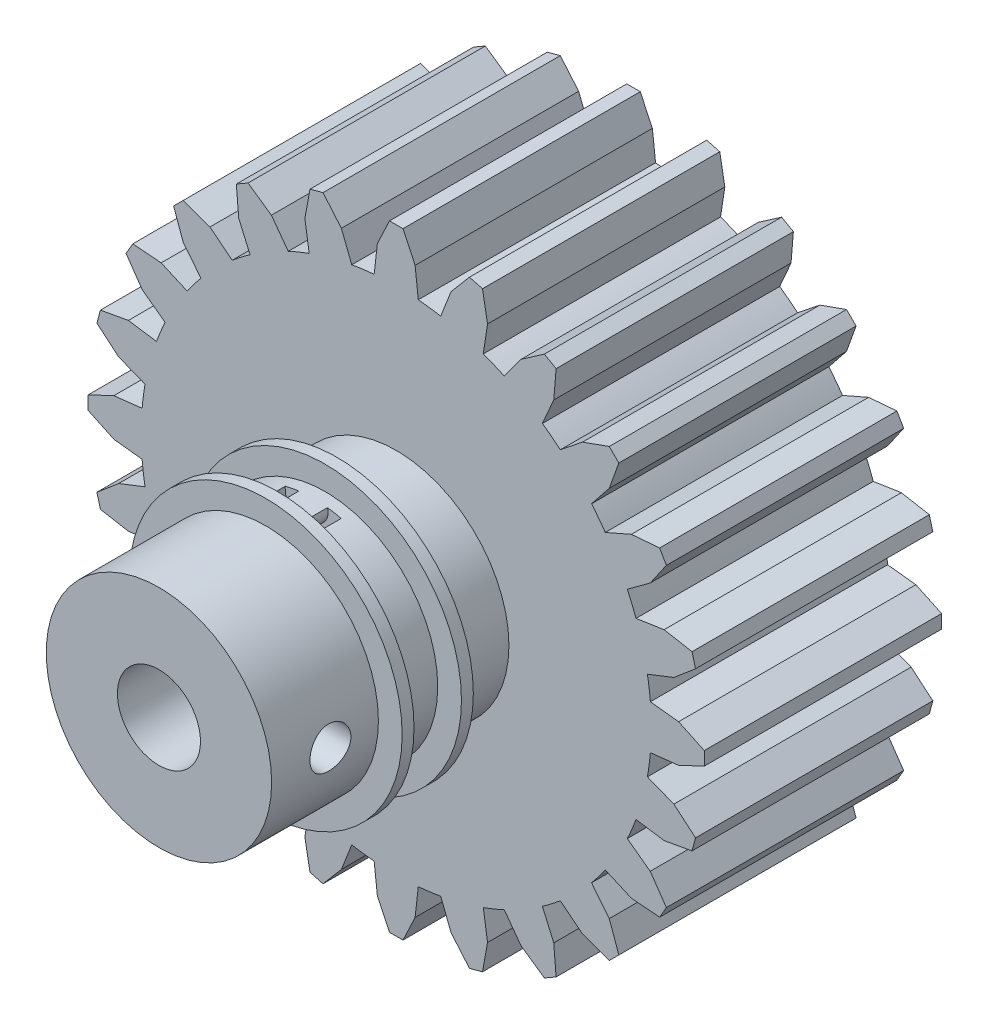
SolidWorks part; units mm, degrees
ref_plane "Plan de face" through (0, 0, 0) normal (0, 0, 1) x (1, 0, 0)
ref_plane "Plan de dessus" through (0, 0, 0) normal (0, 1, 0) x (1, 0, 0)
ref_plane "Plan de droite" through (0, 0, 0) normal (1, 0, 0) x (0, 0, -1)
sketch "Esquisse1" plane through (0, 0, 0) normal (0, 0, 1) x (1, 0, 0)
  line L0 (-1.8585, 21.4195) -> (-1.5915, 23.7996)
  line L1 (0, 2.2889) -> (0, 19223.5431) construction
  line L2 (-1.5915, 23.7996) -> (-0.5695, 25.9656)
  line L3 (-0.5695, 25.9656) -> (0.5695, 25.9656)
  line L4 (0, 0) -> (50000, 0) construction
  line L5 (1.8585, 21.4195) -> (1.5915, 23.7996)
  line L6 (1.5915, 23.7996) -> (0.5695, 25.9656)
  line L7 (3.7486, 21.1707) -> (4.6225, 23.4006)
  line L8 (4.6225, 23.4006) -> (6.1703, 25.2282)
  line L9 (7.6971, 22.5767) -> (7.2705, 24.9334)
  line L10 (7.339, 20.2087) -> (7.6971, 22.5767)
  line L11 (6.1703, 25.2282) -> (7.2705, 24.9334)
  line L12 (9.1003, 19.4791) -> (10.5215, 21.4068)
  line L13 (10.5215, 21.4068) -> (12.4896, 22.7716)
  line L14 (13.2781, 19.8153) -> (13.476, 22.2021)
  line L15 (12.3193, 17.6206) -> (13.2781, 19.8153)
  line L16 (12.4896, 22.7716) -> (13.476, 22.2021)
  line L17 (13.8317, 16.46) -> (15.7035, 17.9542)
  line L18 (15.7035, 17.9542) -> (17.9577, 18.7631)
  line L19 (17.9542, 15.7035) -> (18.7631, 17.9577)
  line L20 (16.46, 13.8317) -> (17.9542, 15.7035)
  line L21 (17.9577, 18.7631) -> (18.7631, 17.9577)
  line L22 (17.6206, 12.3193) -> (19.8153, 13.2781)
  line L23 (19.8153, 13.2781) -> (22.2021, 13.476)
  line L24 (21.4068, 10.5215) -> (22.7716, 12.4896)
  line L25 (19.4791, 9.1003) -> (21.4068, 10.5215)
  line L26 (22.2021, 13.476) -> (22.7716, 12.4896)
  line L27 (20.2087, 7.339) -> (22.5767, 7.6971)
  line L28 (22.5767, 7.6971) -> (24.9334, 7.2705)
  line L29 (23.4006, 4.6225) -> (25.2282, 6.1703)
  line L30 (21.1707, 3.7486) -> (23.4006, 4.6225)
  line L31 (24.9334, 7.2705) -> (25.2282, 6.1703)
  line L32 (21.4195, 1.8585) -> (23.7996, 1.5915)
  line L33 (23.7996, 1.5915) -> (25.9656, 0.5695)
  line L34 (23.7996, -1.5915) -> (25.9656, -0.5695)
  line L35 (21.4195, -1.8585) -> (23.7996, -1.5915)
  line L36 (25.9656, 0.5695) -> (25.9656, -0.5695)
  line L37 (21.1707, -3.7486) -> (23.4006, -4.6225)
  line L38 (23.4006, -4.6225) -> (25.2282, -6.1703)
  line L39 (22.5767, -7.6971) -> (24.9334, -7.2705)
  line L40 (20.2087, -7.339) -> (22.5767, -7.6971)
  line L41 (25.2282, -6.1703) -> (24.9334, -7.2705)
  line L42 (19.4791, -9.1003) -> (21.4068, -10.5215)
  line L43 (21.4068, -10.5215) -> (22.7716, -12.4896)
  line L44 (19.8153, -13.2781) -> (22.2021, -13.476)
  line L45 (17.6206, -12.3193) -> (19.8153, -13.2781)
  line L46 (22.7716, -12.4896) -> (22.2021, -13.476)
  line L47 (16.46, -13.8317) -> (17.9542, -15.7035)
  line L48 (17.9542, -15.7035) -> (18.7631, -17.9577)
  line L49 (15.7035, -17.9542) -> (17.9577, -18.7631)
  line L50 (13.8317, -16.46) -> (15.7035, -17.9542)
  line L51 (18.7631, -17.9577) -> (17.9577, -18.7631)
  line L52 (12.3193, -17.6206) -> (13.2781, -19.8153)
  line L53 (13.2781, -19.8153) -> (13.476, -22.2021)
  line L54 (10.5215, -21.4068) -> (12.4896, -22.7716)
  line L55 (9.1003, -19.4791) -> (10.5215, -21.4068)
  line L56 (13.476, -22.2021) -> (12.4896, -22.7716)
  line L57 (7.339, -20.2087) -> (7.6971, -22.5767)
  line L58 (7.6971, -22.5767) -> (7.2705, -24.9334)
  line L59 (4.6225, -23.4006) -> (6.1703, -25.2282)
  line L60 (3.7486, -21.1707) -> (4.6225, -23.4006)
  line L61 (7.2705, -24.9334) -> (6.1703, -25.2282)
  line L62 (1.8585, -21.4195) -> (1.5915, -23.7996)
  line L63 (1.5915, -23.7996) -> (0.5695, -25.9656)
  line L64 (-1.5915, -23.7996) -> (-0.5695, -25.9656)
  line L65 (-1.8585, -21.4195) -> (-1.5915, -23.7996)
  line L66 (0.5695, -25.9656) -> (-0.5695, -25.9656)
  line L67 (-3.7486, -21.1707) -> (-4.6225, -23.4006)
  line L68 (-4.6225, -23.4006) -> (-6.1703, -25.2282)
  line L69 (-7.6971, -22.5767) -> (-7.2705, -24.9334)
  line L70 (-7.339, -20.2087) -> (-7.6971, -22.5767)
  line L71 (-6.1703, -25.2282) -> (-7.2705, -24.9334)
  line L72 (-9.1003, -19.4791) -> (-10.5215, -21.4068)
  line L73 (-10.5215, -21.4068) -> (-12.4896, -22.7716)
  line L74 (-13.2781, -19.8153) -> (-13.476, -22.2021)
  line L75 (-12.3193, -17.6206) -> (-13.2781, -19.8153)
  line L76 (-12.4896, -22.7716) -> (-13.476, -22.2021)
  line L77 (-13.8317, -16.46) -> (-15.7035, -17.9542)
  line L78 (-15.7035, -17.9542) -> (-17.9577, -18.7631)
  line L79 (-17.9542, -15.7035) -> (-18.7631, -17.9577)
  line L80 (-16.46, -13.8317) -> (-17.9542, -15.7035)
  line L81 (-17.9577, -18.7631) -> (-18.7631, -17.9577)
  line L82 (-17.6206, -12.3193) -> (-19.8153, -13.2781)
  line L83 (-19.8153, -13.2781) -> (-22.2021, -13.476)
  line L84 (-21.4068, -10.5215) -> (-22.7716, -12.4896)
  line L85 (-19.4791, -9.1003) -> (-21.4068, -10.5215)
  line L86 (-22.2021, -13.476) -> (-22.7716, -12.4896)
  line L87 (-20.2087, -7.339) -> (-22.5767, -7.6971)
  line L88 (-22.5767, -7.6971) -> (-24.9334, -7.2705)
  line L89 (-23.4006, -4.6225) -> (-25.2282, -6.1703)
  line L90 (-21.1707, -3.7486) -> (-23.4006, -4.6225)
  line L91 (-24.9334, -7.2705) -> (-25.2282, -6.1703)
  line L92 (-21.4195, -1.8585) -> (-23.7996, -1.5915)
  line L93 (-23.7996, -1.5915) -> (-25.9656, -0.5695)
  line L94 (-23.7996, 1.5915) -> (-25.9656, 0.5695)
  line L95 (-21.4195, 1.8585) -> (-23.7996, 1.5915)
  line L96 (-25.9656, -0.5695) -> (-25.9656, 0.5695)
  line L97 (-21.1707, 3.7486) -> (-23.4006, 4.6225)
  line L98 (-23.4006, 4.6225) -> (-25.2282, 6.1703)
  line L99 (-22.5767, 7.6971) -> (-24.9334, 7.2705)
  line L100 (-20.2087, 7.339) -> (-22.5767, 7.6971)
  line L101 (-25.2282, 6.1703) -> (-24.9334, 7.2705)
  line L102 (-19.4791, 9.1003) -> (-21.4068, 10.5215)
  line L103 (-21.4068, 10.5215) -> (-22.7716, 12.4896)
  line L104 (-19.8153, 13.2781) -> (-22.2021, 13.476)
  line L105 (-17.6206, 12.3193) -> (-19.8153, 13.2781)
  line L106 (-22.7716, 12.4896) -> (-22.2021, 13.476)
  line L107 (-16.46, 13.8317) -> (-17.9542, 15.7035)
  line L108 (-17.9542, 15.7035) -> (-18.7631, 17.9577)
  line L109 (-15.7035, 17.9542) -> (-17.9577, 18.7631)
  line L110 (-13.8317, 16.46) -> (-15.7035, 17.9542)
  line L111 (-18.7631, 17.9577) -> (-17.9577, 18.7631)
  line L112 (-12.3193, 17.6206) -> (-13.2781, 19.8153)
  line L113 (-13.2781, 19.8153) -> (-13.476, 22.2021)
  line L114 (-10.5215, 21.4068) -> (-12.4896, 22.7716)
  line L115 (-9.1003, 19.4791) -> (-10.5215, 21.4068)
  line L116 (-13.476, 22.2021) -> (-12.4896, 22.7716)
  line L117 (-7.339, 20.2087) -> (-7.6971, 22.5767)
  line L118 (-7.6971, 22.5767) -> (-7.2705, 24.9334)
  line L119 (-4.6225, 23.4006) -> (-6.1703, 25.2282)
  line L120 (-3.7486, 21.1707) -> (-4.6225, 23.4006)
  line L121 (-7.2705, 24.9334) -> (-6.1703, 25.2282)
  arc A0 (-7.339, 20.2087) -> (-9.1003, 19.4791) centre (0, 0) ccw
  circle A1 centre (0, 0) radius 3.5
  arc A2 (-1.8585, 21.4195) -> (-3.7486, 21.1707) centre (0, 0) ccw
  arc A3 (3.7486, 21.1707) -> (1.8585, 21.4195) centre (0, 0) ccw
  arc A4 (9.1003, 19.4791) -> (7.339, 20.2087) centre (0, 0) ccw
  arc A5 (13.8317, 16.46) -> (12.3193, 17.6206) centre (0, 0) ccw
  arc A6 (17.6206, 12.3193) -> (16.46, 13.8317) centre (0, 0) ccw
  arc A7 (20.2087, 7.339) -> (19.4791, 9.1003) centre (0, 0) ccw
  arc A8 (21.4195, 1.8585) -> (21.1707, 3.7486) centre (0, 0) ccw
  arc A9 (21.1707, -3.7486) -> (21.4195, -1.8585) centre (0, 0) ccw
  arc A10 (19.4791, -9.1003) -> (20.2087, -7.339) centre (0, 0) ccw
  arc A11 (16.46, -13.8317) -> (17.6206, -12.3193) centre (0, 0) ccw
  arc A12 (12.3193, -17.6206) -> (13.8317, -16.46) centre (0, 0) ccw
  arc A13 (7.339, -20.2087) -> (9.1003, -19.4791) centre (0, 0) ccw
  arc A14 (1.8585, -21.4195) -> (3.7486, -21.1707) centre (0, 0) ccw
  arc A15 (-3.7486, -21.1707) -> (-1.8585, -21.4195) centre (0, 0) ccw
  arc A16 (-9.1003, -19.4791) -> (-7.339, -20.2087) centre (0, 0) ccw
  arc A17 (-13.8317, -16.46) -> (-12.3193, -17.6206) centre (0, 0) ccw
  arc A18 (-17.6206, -12.3193) -> (-16.46, -13.8317) centre (0, 0) ccw
  arc A19 (-20.2087, -7.339) -> (-19.4791, -9.1003) centre (0, 0) ccw
  arc A20 (-21.4195, -1.8585) -> (-21.1707, -3.7486) centre (0, 0) ccw
  arc A21 (-21.1707, 3.7486) -> (-21.4195, 1.8585) centre (0, 0) ccw
  arc A22 (-19.4791, 9.1003) -> (-20.2087, 7.339) centre (0, 0) ccw
  arc A23 (-16.46, 13.8317) -> (-17.6206, 12.3193) centre (0, 0) ccw
  arc A24 (-12.3193, 17.6206) -> (-13.8317, 16.46) centre (0, 0) ccw
  point P17 (0, 25.9656)
  point P156 (0, 0)
  dimension "D1" = 43
  dimension "D2" = 7
  dimension "D3" = 2.395
  dimension "D4" = 83.6
  dimension "D5" = 1.8585
  dimension "D6" = 2.395
  dimension "D7" = 0.5695
  dimension "D8" = 24
extrude "Boss.-Extru.1" add sketch "Esquisse1" along normal blind 20
sketch "Esquisse2" plane through (0, 0, 20) normal (0, 0, 1) x (1, 0, 0)
  circle A0 centre (0, 0) radius 3.5
  circle A1 centre (0, 0) radius 9.5
  circle A2 centre (0, 0) radius 3.5 construction
  dimension "D1" = 6
extrude "Boss.-Extru.2" add sketch "Esquisse2" along normal blind 20
sketch "Esquisse3" plane through (0, 0, 0) normal (1, 0, 0) x (0, -1, 0)
  line L0 (-7.5, -35.0467) -> (49992.5, -35.0467) construction
  line L2 (0, -30) -> (0, 49970) construction
  line L3 (-9.5, -40) -> (9.5, -40) construction
  circle A0 centre (0, -35.0467) radius 1.725
  point P13 (0, -40)
  dimension "D1" = 3.45
extrude "Enlèv. mat.-Extru.1" cut sketch "Esquisse3" along normal blind 10
ref_plane "Plan2" through (0, 0, 25) normal (0, 0, 1) x (1, 0, 0)
ref_plane "Plan3" through (0, 0, 30) normal (0, 0, 1) x (1, 0, 0)
sketch "Esquisse10" plane through (0, 0, 25) normal (0, 0, 1) x (1, 0, 0)
  circle A0 centre (0, 0) radius 11.5
  circle A1 centre (0, 0) radius 9.5
  dimension "D1" = 2
extrude "Boss.-Extru.6" add sketch "Esquisse10" along normal blind 1
sketch "Esquisse11" plane through (0, 0, 30) normal (0, 0, 1) x (1, 0, 0)
  circle A0 centre (0, 0) radius 11.5
  circle A1 centre (0, 0) radius 9.5
  dimension "D1" = 2
extrude "Boss.-Extru.7" add sketch "Esquisse11" along normal blind 1
sketch "Esquisse12" plane through (0, 0, 26) normal (0, 0, 1) x (1, 0, 0)
  circle A0 centre (0, 10.5) radius 0.5
  circle A2 centre (0, 0) radius 11.5 construction
  point P2 (0, 10.6729)
  dimension "D1" = 1
  dimension "D2" = 10.5
extrude "Boss.-Extru.8" [suppressed] add sketch "Esquisse12" along normal up to surface (4 mm away) up to face at (11.5, 0, 30)
sketch "Esquisse13" plane through (0, 0, 26) normal (0, 0, 1) x (1, 0, 0)
  line L0 (0, 0) -> (0, 23.2063) construction
  arc A0 (-1.2077, 9.4229) -> (1.2077, 9.4229) centre (0, 9.0825) ccw
  circle A1 centre (0, 0) radius 9.5 construction
  arc A2 (-2.3563, 9.2031) -> (2.3563, 9.2031) centre (0, 9.0825) ccw
  circle A3 centre (0, 0) radius 9.5 construction
  arc A4 (2.3563, 9.2031) -> (1.2077, 9.4229) centre (0, 0) ccw
  arc A5 (-1.2077, 9.4229) -> (-2.3563, 9.2031) centre (0, 0) ccw
  point P1 (-1.2356, 9.4193)
  point P8 (-1.8019, 9.3275)
  point P14 (-0.9454, 9.4528)
  point P15 (-2.4726, 9.1726)
  point P16 (1.8967, 9.4133)
  point P17 (0, 9.0825)
  point P18 (-1.2077, 9.4229)
extrude "Enlèv. mat.-Extru.2" cut sketch "Esquisse13" along normal offset from surface (2 mm away) 1 from offset 1 up to face at (11.5, 0, 30)
ref_plane "Plan1" [suppressed] through (9.5, 0, 0) normal (1, 0, 0) x (0, 0, -1)
sketch "Esquisse4" [suppressed] plane through (9.5, 0, 0) normal (1, 0, 0) x (0, 0, -1)
  line L0 (0, 0) -> (50000, 0) construction
  circle A0 centre (-22.0248, 0) radius 0.5
  point P5 (-22.0248, 0)
  dimension "D1" = 1
sketch "Esquisse5" [suppressed] plane through (0, 0, 0) normal (0, 1, 0) x (1, 0, 0)
  line L0 (9.5, -22.0248) -> (11.4603, -22.0248)
  line L1 (9.5, -200000) -> (9.5, 250000) construction
  line L3 (11.4603, -31.5406) -> (9.5, -31.5406)
  arc A0 (11.855, -22.8316) -> (11.855, -30.7337) centre (16.9379, -26.7827) ccw
  arc A1 (11.855, -30.7337) -> (11.4603, -31.5406) centre (11.4603, -31.0406) cw
  arc A2 (11.4603, -22.0248) -> (11.855, -22.8316) centre (11.4603, -22.5248) cw
  point P7 (12.601, -21.5218)
  point P9 (10.5, -26.7827)
  point P14 (0, 0)
  dimension "D2" = 0.5
  dimension "D1" = 1
sweep "Balayage4" [suppressed] add profiles "Esquisse4" path "Esquisse5"
